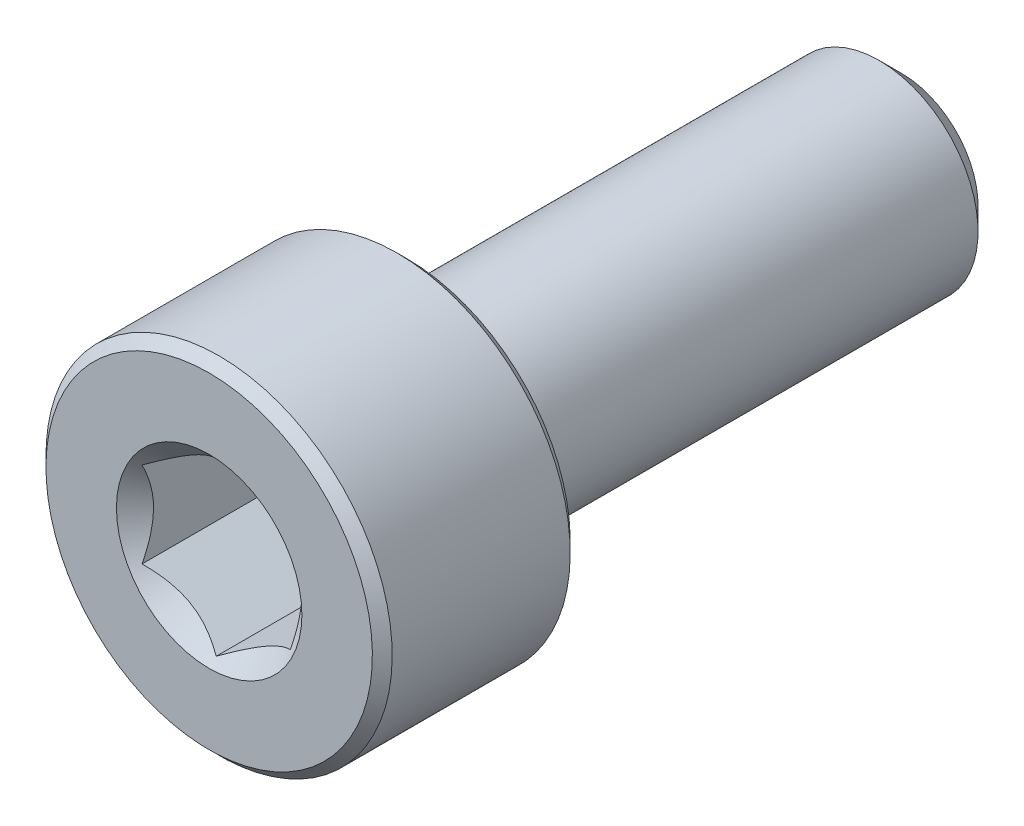
SolidWorks part; units mm, degrees
ref_plane "Front Plane" through (0, 0, 0) normal (0, 0, 1) x (1, 0, 0)
ref_plane "Top Plane" through (0, 0, 0) normal (0, 1, 0) x (1, 0, 0)
ref_plane "Right Plane" through (0, 0, 0) normal (1, 0, 0) x (0, 0, -1)
sketch "Sketch1" plane through (0, 0, 0) normal (1, 0, 0) x (0, 0, -1)
  line L0 (-7, 0) -> (7, 0) construction
  line L1 (7, 0) -> (7, 1.5453) construction
  line L2 (7, 1.5453) -> (6.5453, 2) construction
  line L3 (6.5453, 2) -> (6.475, 2) construction
  line L4 (6.475, 2) -> (-3, 2) construction
  line L5 (-3, 2) -> (-3, 3.5) construction
  line L6 (-3, 3.5) -> (-7, 3.5) construction
  line L7 (-7, 3.5) -> (-7, 0) construction
  line L8 (7, 1.5453) -> (7, 2) construction
  line L9 (6.9562, 2.0758) -> (7.3062, 1.4696) construction
  line L10 (7.3062, 1.4696) -> (7.6562, 2.0758) construction
  line L11 (7.6562, 2.0758) -> (6.9562, 2.0758) construction
  line L12 (7.3062, 2.0758) -> (7.3062, 2) construction
  line L13 (7.3062, 1.4696) -> (7.3062, 1.5453) construction
  line L14 (7.2625, 1.5453) -> (7.35, 1.5453) construction
  line L15 (7, 2) -> (7.6125, 2) construction
  line L16 (6.9781, 2.0379) -> (7.6344, 2.0379) construction
  line L17 (7, 0) -> (7, -2) construction
  line L18 (-3.2, 3.5) -> (-3, 3.3) construction
  line L19 (-6.8, 3.5) -> (-7, 3.3) construction
  line L20 (-3, 2) -> (-3, 0) construction
  line L21 (-3, 1) -> (0.3333, 1) construction
  line L22 (0.3333, 1) -> (3.6667, 1) construction
  line L23 (3.6667, 1) -> (7, 1) construction
  line L24 (0.3333, 1) -> (0.3333, 2) construction
  line L25 (0.3333, 2) -> (0.3333, 3.5) construction
  line L26 (3.6667, 1) -> (3.6667, 3.5) construction
  point P0 (-7, 1.5)
  point P3 (5.25, 2)
  point P4 (0, 0)
  point P18 (3.6667, 2)
  point P22 (7.3062, 1.5453)
  point P24 (6.475, 2)
  point P25 (7.3062, 2)
  point P28 (7.3062, 2.0379)
  point P29 (5.25, -2)
  point P30 (0.3333, 2)
  point P31 (-5, 3.5)
  point P37 (-3.7, 3.5)
  point P38 (-6.7, 3.5)
  point P45 (0.3333, 1)
  point P46 (3.6667, 1)
  dimension "D2" = 0.0875
  dimension "D7" = 0.2
  dimension "D8" = 0.2
  dimension "D9" = 0.2
  dimension "D10" = 0.1
  dimension "D11" = 0.5
  dimension "Drive Size" = 3
  dimension "Head Diameter" = 7
  dimension "Head Height" = 4
  dimension "Thread Pitch" = 0.7
  dimension "Thread Size" = 4
  dimension "Length" = 10
  dimension "D12" = 0.525
  dimension "D4" = 1.75
  dimension "D3" = 45
sketch "Sketch2" plane through (0, 0, 0) normal (1, 0, 0) x (0, 0, -1)
  line L0 (-7, 0) -> (-7, 3.3)
  line L1 (-6.8, 3.5) -> (-3.2, 3.5)
  line L2 (-3, 3.3) -> (-3, 2.2)
  line L4 (6.5453, 2) -> (7, 1.5453)
  line L5 (7, 1.5453) -> (7, 0)
  line L6 (-3, 3.5) -> (-7, 3.5) construction
  line L7 (7, 0) -> (-7, 0)
  line L8 (-6.8, 3.5) -> (-7, 3.3) construction
  line L10 (-6.8, 3.5) -> (-7, 3.3)
  line L14 (-3.2, 3.5) -> (-3, 3.3) construction
  line L16 (-3.2, 3.5) -> (-3, 3.3)
  line L17 (-3, 2) -> (-3, 3.5) construction
  line L19 (-2.8, 2) -> (6.5453, 2)
  line L20 (6.475, 2) -> (-3, 2) construction
  arc A1 (-3, 2.2) -> (-2.8, 2) centre (-2.8, 2.2) ccw
  dimension "D3" = 0.2
revolve "Revolve1" add sketch "Sketch2" angle 360 about L7
sketch "Sketch3" plane through (0, 0, 7) normal (0, 0, 1) x (1, 0, 0)
  line L1 (1.5, -0.866) -> (1.5, 0.866)
  line L2 (1.5, 0.866) -> (0, 1.7321)
  line L3 (0, 1.7321) -> (-1.5, 0.866)
  line L4 (-1.5, 0.866) -> (-1.5, -0.866)
  line L5 (-1.5, -0.866) -> (0, -1.7321)
  line L6 (0, -1.7321) -> (1.5, -0.866)
  circle A0 centre (0, 0) radius 1.5 construction
  circle A1 centre (0, 0) radius 3.5 construction
  circle A2 centre (0, 0) radius 3.5 construction
  circle A3 centre (0, 0) radius 1.7321 construction
  point P13 (0, 0)
extrude "Cut-Extrude1" cut sketch "Sketch3" against normal offset from surface (3 mm away) 1 up to face at (0, 3.3, 3)
sketch "Sketch4" plane through (0, 0, 7) normal (0, 0, 1) x (1, 0, 0)
  circle A0 centre (0, 0) radius 1.875
  dimension "D1" = 3.75
extrude "Cut-Extrude2" cut sketch "Sketch4" against normal up to vertex (2 mm away) draft 45 up to point (0, 3.5, 5)
sketch "Sketch11" plane through (0, 0, 0) normal (1, 0, 0) x (0, 0, -1)
  line L0 (-7, 0) -> (7, 0) construction
  line L1 (-7, 0) -> (7, 0) construction
  line L2 (-1.125, 0) -> (-1.125, 2) construction
  line L3 (6.475, 2) -> (-3, 2) construction
  line L4 (5.125, 0) -> (5.125, 2) construction
  line L6 (7, 1.5453) -> (7, 2) construction
  point P2 (-1.125, 0)
  point P3 (5.125, 0)
  dimension "D1" = 1.875
  dimension "D2" = 1.875
sketch "Sketch8" [suppressed] plane through (0, 0, 0) normal (1, 0, 0) x (0, 0, -1)
  line L0 (-3, 0) -> (-3, 2)
  line L1 (-2.8, -2) -> (-2.8, 2) construction
  line L2 (-3, 2) -> (-2.8, 2)
  line L4 (-2.8, 2) -> (-1.6453, 0)
  line L5 (-1.6453, 0) -> (-3, 0)
  line L6 (6.475, 2) -> (-3, 2) construction
  line L7 (-7, 0) -> (7, 0) construction
  dimension "D1" = 60
equation "\"D2@Sketch1\" = \"Thread Pitch@Sketch1\" / 8"
equation "\"D7@Sketch1\" = \"Head Height@Sketch1\" * .05"
equation "\"D8@Sketch1\"=\"D7@Sketch1\""
equation "\"D9@Sketch1\"=\"D7@Sketch1\""
equation "\"D10@Sketch1\"=\"D7@Sketch1\"/2"
equation "\"D11@Sketch1\"=\"D10@Sketch1\"*5"
equation "\"D4@Sketch1\"=\"Thread Pitch@Sketch1\"*2.5"
equation "\"D12@Sketch1\"=\"Thread Pitch@Sketch1\"*.75"
equation "\"D3@Sketch2\" = \"Thread Size@Sketch1\" * 0.05"
equation "\"D1@Sketch11\"=\"Length@Sketch1\"*0.1875"
equation "\"D2@Sketch11\"=\"D1@Sketch11\""
equation "\"D1@Sketch4\"=\"Drive Size@Sketch1\"*1.25"
